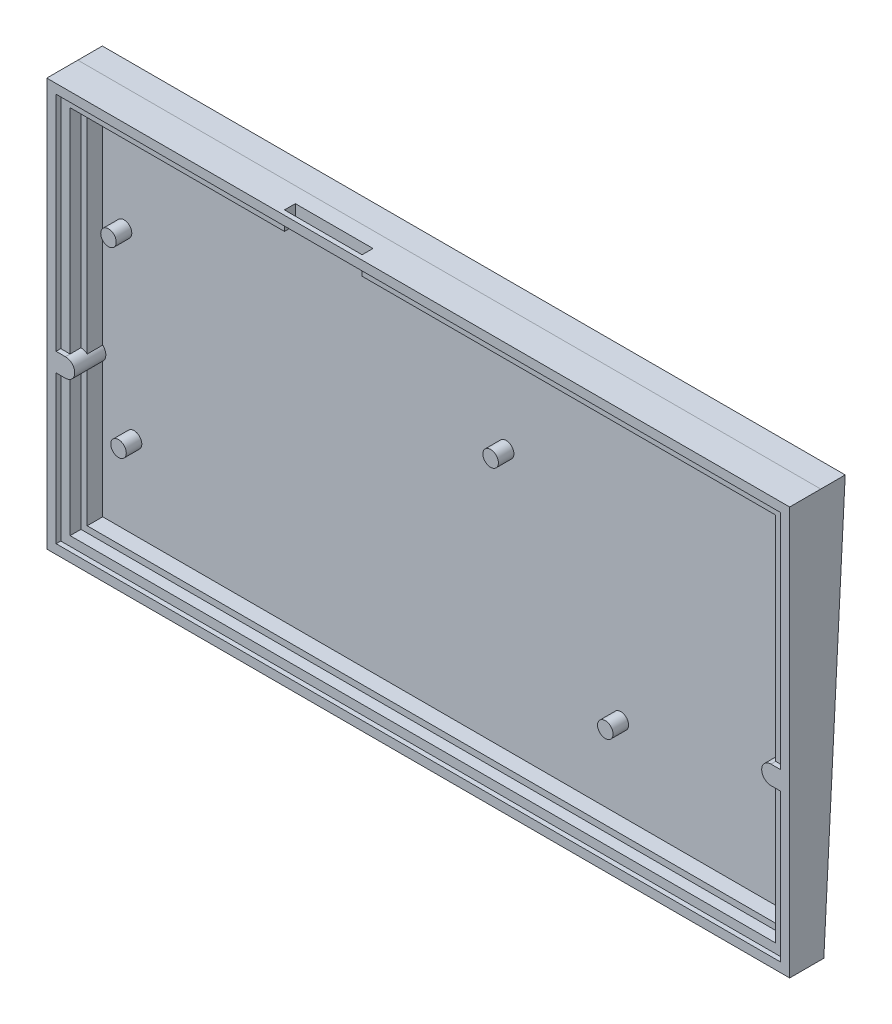
SolidWorks part; units mm, degrees
ref_plane "前视基准面" through (0, 0, 0) normal (0, 0, 1) x (1, 0, 0)
ref_plane "上视基准面" through (0, 0, 0) normal (0, 1, 0) x (1, 0, 0)
ref_plane "右视基准面" through (0, 0, 0) normal (1, 0, 0) x (0, 0, -1)
sketch "Model" plane through (0, 0, 0) normal (0, 0, 1) x (1, 0, 0)
  line L0 (675.8758, 289.5359) -> (675.8758, 217.8613)
  line L1 (672.8758, 286.5359) -> (672.8758, 217.8613)
  line L2 (670.8758, 284.5359) -> (670.8758, 217.0974)
  line L3 (675.8758, 211.8613) -> (675.8758, 164.2356)
  line L4 (675.8758, 164.2356) -> (442.7618, 164.2356)
  line L5 (678.8758, 292.5345) -> (678.8758, 161.2356)
  line L6 (678.8758, 161.2356) -> (439.7618, 161.2356)
  line L7 (672.8758, 211.8613) -> (672.8758, 167.2356)
  line L8 (672.8758, 167.2356) -> (445.7618, 167.2356)
  line L9 (670.8758, 212.6252) -> (670.8758, 169.2356)
  line L10 (670.8758, 169.2356) -> (447.7618, 169.2356)
  line L11 (442.7618, 289.5359) -> (675.8758, 289.5359)
  line L12 (445.7618, 286.5359) -> (672.8758, 286.5359)
  line L13 (447.7618, 284.5359) -> (670.8758, 284.5359)
  line L14 (442.7618, 164.2356) -> (442.7618, 211.8613)
  line L15 (445.7618, 167.2356) -> (445.7618, 211.8613)
  line L16 (447.7618, 169.2356) -> (447.7618, 212.6252)
  line L17 (442.7618, 217.8613) -> (442.7618, 289.5359)
  line L18 (439.7618, 161.2356) -> (439.7618, 292.5359)
  line L19 (445.7618, 217.8613) -> (445.7618, 286.5359)
  line L20 (447.7618, 217.0974) -> (447.7618, 284.5359)
  line L21 (675.8758, 211.8613) -> (672.8758, 211.8613)
  line L22 (675.8758, 217.8613) -> (672.8758, 217.8613)
  line L23 (442.7618, 217.8613) -> (445.7618, 217.8613)
  line L24 (445.7618, 211.8613) -> (442.7618, 211.8613)
  line L25 (675.8758, 217.8613) -> (675.8758, 289.5359)
  line L26 (439.7618, 161.2356) -> (678.8758, 161.2356)
  line L27 (439.7618, 161.2356) -> (439.7618, 292.5345)
  line L28 (514.7618, 286.5359) -> (539.7618, 286.5359)
  line L29 (439.7618, 292.5345) -> (678.8758, 292.5345)
  line L30 (439.7618, 292.5359) -> (678.8758, 292.5345)
  line L31 (678.8758, 161.2356) -> (678.8758, 292.5345)
  arc A0 (672.8758, 217.8613) -> (672.8758, 211.8613) centre (672.8758, 214.8613) ccw
  arc A1 (445.7618, 211.8613) -> (445.7618, 217.8613) centre (445.7618, 214.8613) ccw
  circle A2 centre (457.8498, 195.8116) radius 1.5
  circle A3 centre (577.6247, 252.9613) radius 1.5
  circle A4 centre (614.5337, 195.8116) radius 1.5
extrude "凸台-拉伸2" add sketch "Model" along normal blind 10 contours L29 L18 L6 L5 A1 L23 L17 L11 L0 L22 A0 L21 L3 L4 L14 L24 region at (676.1479, 226.8851, 0)
extrude "凸台-拉伸3" add sketch "Model<4>" along normal blind 8.5 contours L15 L24 L14 L4 L3 L21 L7 L8 | L17 L23 L19 L12 L1 L22 L0 L11 region at (673.437, 253.6986, 0) region at (674.3758, 209.482, 0)
sketch "Model<4>" plane through (0, 0, 0) normal (0, 0, 1) x (1, 0, 0) same geometry as "Model"
extrude "凸台-拉伸4" add sketch "Model<5>" along normal blind 5 contours A1 L15 L8 L7 A0 L9 L10 L16 | A1 L20 L13 L2 A0 L1 L12 L19 region at (670.9579, 219.8824, 0) region at (670.979, 209.8952, 0)
sketch "Model<5>" plane through (0, 0, 0) normal (0, 0, 1) x (1, 0, 0) same geometry as "Model"
sketch "草图3" plane through (0, 0, 0) normal (0, 0, -1) x (-1, 0, 0)
  circle A0 centre (-577.6247, 252.9613) radius 2.5
  circle A1 centre (-614.5337, 195.8116) radius 2.5
  circle A2 centre (-457.8498, 195.8116) radius 2.5
  circle A3 centre (-454.6247, 252.9613) radius 2.5
  dimension "D1" = 123
extrude "凸台-拉伸5" add sketch "草图3" against normal blind 5 separate body
sketch "草图4" plane through (439.7618, 0, 0) normal (-1, 0, 0) x (0, 0, 1)
  line L1 (-7.8812, 292.5361) -> (-1, 161.2356)
  line L5 (0, 161.2356) -> (0, 292.5345)
  line L8 (-7.8812, 292.5361) -> (0, 292.5345)
  line L9 (0, 161.2356) -> (-1, 161.2356)
  point P3 (-10.2492, 159.7149)
  dimension "D1" = 3
  dimension "D2" = 11
extrude "凸台-拉伸6" add sketch "草图4" against normal up to surface (239.114 mm away) up to face at (678.8758, 226.8851, 5)
sketch "草图5" plane through (0, 0, 8.5) normal (0, 0, 1) x (1, 0, 0)
  line L0 (445.7618, 286.5359) -> (672.8758, 286.5359) construction
  line L1 (539.7618, 286.5359) -> (514.7618, 286.5359)
  line L2 (539.7618, 286.5359) -> (539.7618, 292.5345)
  line L3 (539.7618, 292.5345) -> (514.7618, 292.5345)
  line L4 (514.7618, 286.5359) -> (514.7618, 292.5345)
  line L5 (439.7618, 292.5345) -> (678.8758, 292.5345) construction
  dimension "D1" = 25
  dimension "D2" = 69
extrude "切除-拉伸1" cut sketch "草图5" against normal blind 3.5
